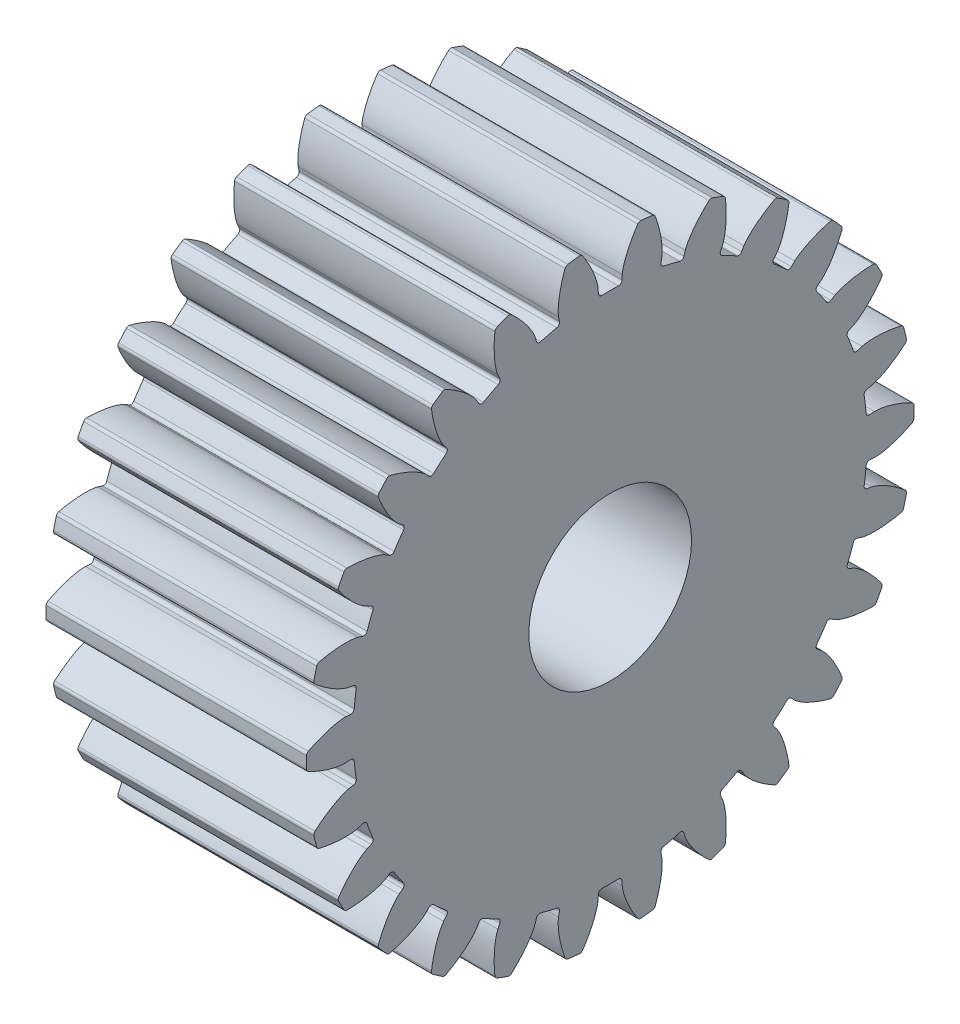
SolidWorks part; units mm, degrees
ref_plane "Front Plane" through (0, 0, 0) normal (1, 0, 0) x (0, 1, 0)
ref_plane "Top Plane" through (0, 0, 0) normal (0, 0, 1) x (0, 1, 0)
ref_plane "Right Plane" through (0, 0, 0) normal (0, 1, 0) x (-1, 0, 0)
sketch "Sketch2" plane through (0, 0, 0) normal (1, 0, 0) x (0, 1, 0)
  circle A0 centre (0, 0) radius 3.9688
  circle A1 centre (0, 0) radius 14.8167
  dimension "D1" = 7.9375
  dimension "D2" = 29.6333
extrude "Gear Width Extrude" add sketch "Sketch2" along normal blind 12.7
sketch "Sketch3" plane through (0, 0, 0) normal (1, 0, 0) x (0, 1, 0)
  line L0 (-14.8167, 0) -> (14.8167, 0) construction
  line L1 (0, 14.8167) -> (0, -14.8167) construction
  line L2 (0, 0) -> (12.9152, 0.5882) construction
  line L5 (12.5338, 0) -> (14.8167, 0)
  line L6 (12.9152, 0.5882) -> (12.5209, 0.5702)
  circle A0 centre (0, 0) radius 12.5338 construction
  circle A1 centre (0, 0) radius 12.9286 construction
  circle A2 centre (0, 0) radius 13.7583 construction
  circle A3 centre (0, 0) radius 14.8167 construction
  arc A7 (14.7499, 1.4052) -> (14.8167, 0) centre (0, 0) cw
  arc A8 (12.5209, 0.5702) -> (12.5338, 0) centre (0, 0) cw
  spline S0 degree 4 poles (12.9152, 0.5882) (12.9182, 0.5884) (12.9266, 0.589) (12.9524, 0.5915) (13.0033, 0.5985) (13.0658, 0.61) (13.1375, 0.6259) (13.2064, 0.6434) (13.2652, 0.6597) (13.3236, 0.6772) (13.3817, 0.6958) (13.4518, 0.7196) (13.5357, 0.7499) (13.6332, 0.788) (13.7433, 0.8343) (13.8548, 0.8849) (13.9641, 0.9373) (14.0738, 0.9935) (14.1795, 1.05) (14.2886, 1.1119) (14.389, 1.1707) (14.5005, 1.2401) (14.5903, 1.2971) (14.7079, 1.376) (14.777, 1.4237) (14.8576, 1.4809) (14.8932, 1.5069) (14.9151, 1.5229) knots 0 0 0 0 0 0.005377 0.015084 0.04661 0.092111 0.119476 0.146842 0.174209 0.201575 0.228941 0.256307 0.307035 0.361767 0.4165 0.471232 0.525964 0.580697 0.635429 0.690161 0.744894 0.799626 0.854358 0.909091 0.954545 1 1 1 1 1 construction
  spline S1 degree 4 poles (12.9152, 0.5882) (12.9182, 0.5884) (12.9266, 0.589) (12.9524, 0.5915) (13.0033, 0.5985) (13.0658, 0.61) (13.1375, 0.6259) (13.2064, 0.6434) (13.2652, 0.6597) (13.3236, 0.6772) (13.3817, 0.6958) (13.4518, 0.7196) (13.5357, 0.7499) (13.6332, 0.788) (13.7433, 0.8343) (13.8548, 0.8849) (13.9641, 0.9373) (14.0738, 0.9935) (14.1795, 1.05) (14.2886, 1.1119) (14.389, 1.1707) (14.5005, 1.2401) (14.5903, 1.2971) (14.6824, 1.3589) (14.7271, 1.3894) (14.7499, 1.4052) knots 0 0 0 0 0 0.005377 0.015084 0.04661 0.092111 0.119476 0.146842 0.174209 0.201575 0.228941 0.256307 0.307035 0.361767 0.4165 0.471232 0.525964 0.580697 0.635429 0.690161 0.744894 0.799626 0.854358 0.909091 0.909091 0.909091 0.909091 0.909091
  dimension "D1" = 27.5167
  dimension "D2" = 25.8572
  dimension "D3" = 25.0677
extrude "Gear Tooth Cut" cut sketch "Sketch3" along normal blind 25.4 contours S1 region at (0, 13.8551, 0.4679)
mirror "Gear Tooth Cut Mirror" about plane through (25.4, 0, 0) normal (0, 0, 1) of "Gear Tooth Cut"
fillet "Tooth Fillets" radius 0.1662 4 edges at (6.35, 14.7499, 1.4052) (6.35, 14.7499, -1.4052) (6.35, 12.5209, 0.5702) (6.35, 12.5209, -0.5702)
pattern_circular "CirPattern1" count 26 over 360 about axis through (0, 0, 0) along (1, 0, 0) of "Gear Tooth Cut", "Gear Tooth Cut Mirror", "Tooth Fillets"
equation "\"DP\"= 24'INPUT: Diametral Pitch"
equation "\"a_Pressure\"= 20'INPUT: Pressure Angle"
equation "\"Z\"= 26'INPUT: Number of Teeth"
equation "\"w_Face\"= 0.5'INPUT: Face Width"
equation "\"d_Bore\"= 5 / 16'INPUT: Bore Diameter"
equation "\"d_Pitch\"= \"Z\" / \"DP\"'Pitch Diameter"
equation "\"Module\"= 1 / \"DP\"'Module"
equation "\"d_Base\"= \"d_Pitch\" * cos ( \"a_Pressure\" )'Base Circle Diameter"
equation "\"Clearance\"= 0.157 / \"DP\"'Clearance"
equation "\"CP\"= pi * \"d_Pitch\" / \"Z\"'Circular Pitch"
equation "\"h_Addendum\"= 1 / \"DP\"'Addendum Depth"
equation "\"h_Dedendum\"= IIF ( \"h_deStandard\" > \"h_deMin\" , \"h_deStandard\" , \"h_deMin\" )'Dedendum Depth"
equation "\"d_Addendum\"= \"d_Pitch\" + ( 2 * \"h_Addendum\" )'Addendum (Tip) Diameter"
equation "\"d_Dedendum\"= \"d_Pitch\" - ( 2 * \"h_Dedendum\" )'Dedendum (Root) Diameter"
equation "\"a_Pitch\"= 360 / \"Z\"'Pitch Angle"
equation "\"a_Alpha\"= ( ( 180 * ( ( \"d_Pitch\" ^ 2 ) - ( \"d_Base\" ^ 2 ) ) ^ 0.5 ) / ( pi * \"d_Base\" ) ) - \"a_Pressure\"'Alpha Angle"
equation "\"a_Beta\"= ( \"a_Pitch\" / 4 ) - \"a_Alpha\"'Beta Angle"
equation "\"ICDP\"= ( ( ( \"d_Addendum\" / 2 ) ^ 2 - ( \"d_Base\" / 2 ) ^ 2 ) ^ 0.5 ) * ( 2 / \"d_Base\" )'Involute Curve Domain Parameter"
equation "\"D1@Sketch2\"=\"d_Bore\""
equation "\"D2@Sketch2\"=\"d_Addendum\""
equation "\"D1@Gear Width Extrude\" = \"w_Face\""
equation "\"D1@Sketch3\"=\"d_Pitch\""
equation "\"D2@Sketch3\"=\"d_Base\""
equation "\"D3@Sketch3\"= \"d_Dedendum\""
equation "\"D1@CirPattern1\"=\"Z\""
equation "\"D1@Tooth Fillets\"=\"Clearance\""
equation "\"h_deStandard\"= ( 1 / \"DP\" ) + \"Clearance\""
equation "\"h_deMin\"= ( \"d_Pitch\" * ( 1 - cos ( \"a_Pressure\" ) ) / 2 ) + \"Clearance\""
